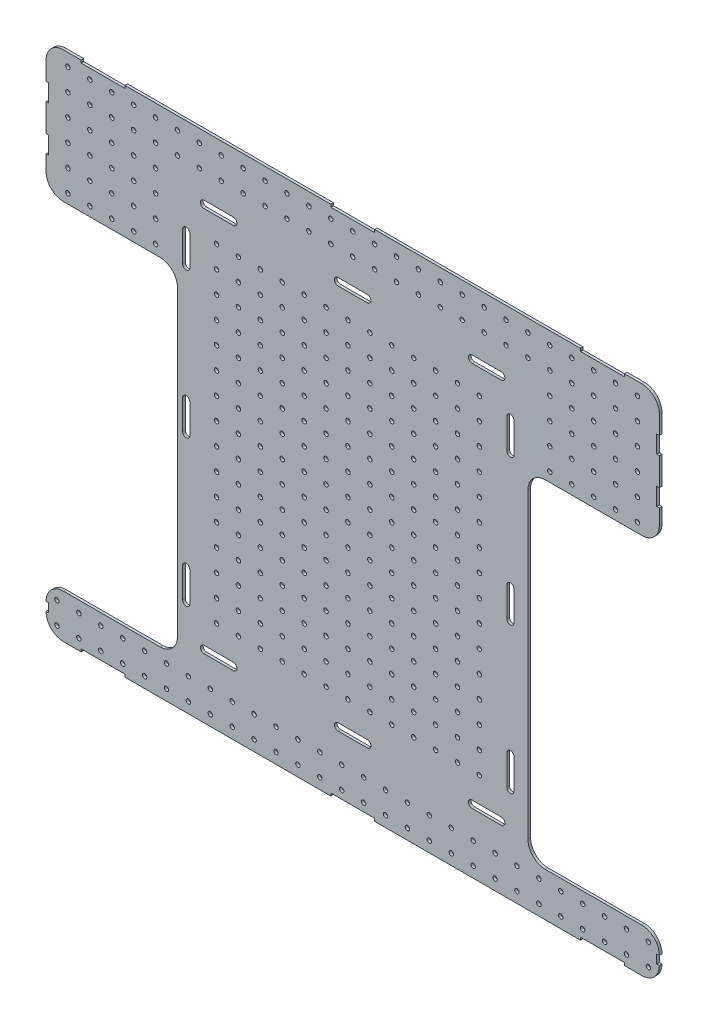
SolidWorks part; units mm, degrees
ref_plane "Front Plane" through (0, 0, 0) normal (0, 0, 1) x (1, 0, 0)
ref_plane "Top Plane" through (0, 0, 0) normal (0, 1, 0) x (1, 0, 0)
ref_plane "Right Plane" through (0, 0, 0) normal (1, 0, 0) x (0, 0, -1)
sketch "Sketch1" plane through (0, 0, 0) normal (0, 0, 1) x (1, 0, 0)
  line L0 (-330, 142.5) -> (-220, 142.5)
  line L1 (-330, -292.5) -> (330, -292.5)
  line L2 (-350, -272.5) -> (-350, -262.5)
  line L3 (-330, 292.5) -> (330, 292.5)
  line L4 (350, -272.5) -> (350, -262.5)
  line L5 (-350, -292.5) -> (-200, -167.1429) construction
  line L6 (-350, 292.5) -> (-343.6073, 287.1575) construction
  line L7 (-330, -242.5) -> (-220, -242.5)
  line L8 (-200, 122.5) -> (-200, -222.5)
  line L9 (200, 122.5) -> (200, -222.5)
  line L10 (220, 142.5) -> (330, 142.5)
  line L11 (220, -242.5) -> (330, -242.5)
  line L12 (-350, 162.5) -> (-350, 272.5)
  line L13 (350, 162.5) -> (350, 272.5)
  line L14 (343.6073, 287.1575) -> (350, 292.5) construction
  line L16 (-200, 122.5) -> (-200, -222.5)
  line L18 (200, 122.5) -> (200, -222.5)
  line L19 (200, -167.1429) -> (350, -292.5) construction
  line L20 (0, 0) -> (165.5771, 138.3751) construction
  line L21 (-101.0703, 84.4659) -> (18.5141, -15.4725) construction
  arc A0 (350, -262.5) -> (330, -242.5) centre (330, -262.5) ccw
  arc A1 (350, -272.5) -> (330, -292.5) centre (330, -272.5) cw
  arc A2 (-330, -292.5) -> (-350, -272.5) centre (-330, -272.5) cw
  arc A3 (-350, -262.5) -> (-330, -242.5) centre (-330, -262.5) cw
  arc A4 (-220, -242.5) -> (-200, -222.5) centre (-220, -222.5) ccw
  arc A5 (200, -222.5) -> (220, -242.5) centre (220, -222.5) ccw
  arc A6 (200, 122.5) -> (220, 142.5) centre (220, 122.5) cw
  arc A7 (350, 162.5) -> (330, 142.5) centre (330, 162.5) cw
  arc A8 (350, 272.5) -> (330, 292.5) centre (330, 272.5) ccw
  arc A9 (-200, 122.5) -> (-220, 142.5) centre (-220, 122.5) ccw
  arc A10 (-330, 142.5) -> (-350, 162.5) centre (-330, 162.5) cw
  arc A11 (-350, 272.5) -> (-330, 292.5) centre (-330, 272.5) cw
  circle A29 centre (-65.0414, 139.6103) radius 2
  circle A30 centre (-35.0414, 139.6103) radius 2
  circle A31 centre (-5.0415, 139.6103) radius 2
  circle A32 centre (24.9585, 139.6103) radius 2
  circle A33 centre (54.9585, 139.6103) radius 2
  circle A34 centre (84.9585, 139.6103) radius 2
  circle A35 centre (114.9584, 139.6103) radius 2
  circle A36 centre (144.9584, 139.6103) radius 2
  circle A41 centre (-95.0827, 108.0718) radius 2
  circle A42 centre (-65.0827, 108.0718) radius 2
  circle A43 centre (-35.0827, 108.0718) radius 2
  circle A44 centre (-5.0827, 108.0718) radius 2
  circle A45 centre (24.9172, 108.0718) radius 2
  circle A46 centre (54.9172, 108.0718) radius 2
  circle A47 centre (84.9172, 108.0718) radius 2
  circle A48 centre (114.9172, 108.0718) radius 2
  circle A49 centre (144.9171, 108.0718) radius 2
  circle A52 centre (-155.1239, 76.5334) radius 2
  circle A53 centre (-125.1239, 76.5334) radius 2
  circle A54 centre (-99.9787, 82.7901) radius 2
  circle A55 centre (-65.124, 76.5334) radius 2
  circle A56 centre (-35.124, 76.5334) radius 2
  circle A57 centre (-5.124, 76.5334) radius 2
  circle A58 centre (24.8759, 76.5334) radius 2
  circle A59 centre (54.8759, 76.5334) radius 2
  circle A60 centre (84.8759, 76.5334) radius 2
  circle A61 centre (114.8759, 76.5334) radius 2
  circle A62 centre (144.8758, 76.5334) radius 2
  circle A65 centre (-155.1652, 44.9949) radius 2
  circle A66 centre (-125.1652, 44.9949) radius 2
  circle A67 centre (-95.1653, 44.9949) radius 2
  circle A68 centre (-65.1653, 44.9949) radius 2
  circle A69 centre (-35.1653, 44.9949) radius 2
  circle A70 centre (-5.1653, 44.9949) radius 2
  circle A71 centre (24.8346, 44.9949) radius 2
  circle A72 centre (54.8346, 44.9949) radius 2
  circle A73 centre (84.8346, 44.9949) radius 2
  circle A74 centre (114.8346, 44.9949) radius 2
  circle A75 centre (144.8345, 44.9949) radius 2
  circle A78 centre (-155.2065, 13.4565) radius 2
  circle A79 centre (-125.2065, 13.4565) radius 2
  circle A80 centre (-95.2065, 13.4565) radius 2
  circle A81 centre (-65.2066, 13.4565) radius 2
  circle A82 centre (-35.2066, 13.4565) radius 2
  circle A83 centre (-5.2066, 13.4565) radius 2
  circle A84 centre (24.7933, 13.4565) radius 2
  circle A85 centre (54.7933, 13.4565) radius 2
  circle A86 centre (84.7933, 13.4565) radius 2
  circle A87 centre (114.7933, 13.4565) radius 2
  circle A88 centre (144.7932, 13.4565) radius 2
  circle A91 centre (-155.2478, -18.082) radius 2
  circle A92 centre (-125.2478, -18.082) radius 2
  circle A93 centre (-95.2478, -18.082) radius 2
  circle A94 centre (-65.2479, -18.082) radius 2
  circle A95 centre (-35.2479, -18.082) radius 2
  circle A96 centre (-5.2479, -18.082) radius 2
  circle A97 centre (18.5779, -13.4735) radius 2
  circle A98 centre (54.752, -18.082) radius 2
  circle A99 centre (84.752, -18.082) radius 2
  circle A100 centre (114.752, -18.082) radius 2
  circle A101 centre (144.7519, -18.082) radius 2
  circle A104 centre (-155.2891, -49.6205) radius 2
  circle A105 centre (-125.2891, -49.6205) radius 2
  circle A106 centre (-95.2891, -49.6205) radius 2
  circle A107 centre (-65.2892, -49.6205) radius 2
  circle A108 centre (-35.2892, -49.6205) radius 2
  circle A109 centre (-5.2892, -49.6205) radius 2
  circle A110 centre (24.7108, -49.6205) radius 2
  circle A111 centre (54.7107, -49.6205) radius 2
  circle A112 centre (84.7107, -49.6205) radius 2
  circle A113 centre (114.7107, -49.6205) radius 2
  circle A114 centre (144.7107, -49.6205) radius 2
  circle A117 centre (-155.3304, -81.1589) radius 2
  circle A118 centre (-125.3304, -81.1589) radius 2
  circle A119 centre (-95.3304, -81.1589) radius 2
  circle A120 centre (-65.3305, -81.1589) radius 2
  circle A121 centre (-35.3305, -81.1589) radius 2
  circle A122 centre (-5.3305, -81.1589) radius 2
  circle A123 centre (24.6695, -81.1589) radius 2
  circle A124 centre (54.6694, -81.1589) radius 2
  circle A125 centre (84.6694, -81.1589) radius 2
  circle A126 centre (114.6694, -81.1589) radius 2
  circle A127 centre (144.6694, -81.1589) radius 2
  circle A130 centre (-155.3717, -112.6974) radius 2
  circle A131 centre (-125.3717, -112.6974) radius 2
  circle A132 centre (-95.3717, -112.6974) radius 2
  circle A133 centre (-65.3718, -112.6974) radius 2
  circle A134 centre (-35.3718, -112.6974) radius 2
  circle A135 centre (-5.3718, -112.6974) radius 2
  circle A136 centre (24.6282, -112.6974) radius 2
  circle A137 centre (54.6281, -112.6974) radius 2
  circle A138 centre (84.6281, -112.6974) radius 2
  circle A139 centre (114.6281, -112.6974) radius 2
  circle A140 centre (144.6281, -112.6974) radius 2
  circle A143 centre (-155.413, -144.2358) radius 2
  circle A144 centre (-125.413, -144.2358) radius 2
  circle A145 centre (-95.413, -144.2358) radius 2
  circle A146 centre (-65.413, -144.2358) radius 2
  circle A147 centre (-35.4131, -144.2358) radius 2
  circle A148 centre (-5.4131, -144.2358) radius 2
  circle A149 centre (24.5869, -144.2358) radius 2
  circle A150 centre (54.5869, -144.2358) radius 2
  circle A151 centre (84.5868, -144.2358) radius 2
  circle A152 centre (114.5868, -144.2358) radius 2
  circle A153 centre (144.5868, -144.2358) radius 2
  circle A156 centre (-155.4543, -175.7743) radius 2
  circle A157 centre (-125.4543, -175.7743) radius 2
  circle A158 centre (-95.4543, -175.7743) radius 2
  circle A159 centre (-65.4543, -175.7743) radius 2
  circle A160 centre (-35.4544, -175.7743) radius 2
  circle A161 centre (-5.4544, -175.7743) radius 2
  circle A162 centre (24.5456, -175.7743) radius 2
  circle A163 centre (54.5456, -175.7743) radius 2
  circle A164 centre (84.5455, -175.7743) radius 2
  circle A165 centre (114.5455, -175.7743) radius 2
  circle A166 centre (144.5455, -175.7743) radius 2
  point P0 (0, 0)
  point P32 (350, 142.5)
  point P40 (-350, 142.5)
  dimension "D6" = 20
  dimension "D7" = 150
  dimension "D1" = 585
  dimension "D2" = 400
  dimension "D3" = 150
  dimension "D4" = 50
  dimension "D5" = 150
extrude "Boss-Extrude1" add sketch "Sketch1" along normal blind 3 contours A11 L12 A10 L0 A9 L8 A4 L7 A3 L2 A2 L1 A1 L4 A0 L11 A5 L9 A6 L10 A7 L13 A8 L3 region at (-0.0004, 19.8849, 0)
sketch "Sketch2" plane through (0, 0, 3) normal (0, 0, 1) x (1, 0, 0)
  line L0 (0, 292.5) -> (0, 224.1) construction
  line L1 (-330, 292.5) -> (330, 292.5) construction
  line L2 (-330, -292.5) -> (330, -292.5) construction
  line L3 (-200, 220) -> (-173.742, 220)
  line L4 (-200, 240) -> (200, 240)
  line L5 (-200, 240) -> (-200, -240)
  line L6 (-200, -240) -> (200, -240)
  line L7 (200, 240) -> (200, -240)
  line L8 (-200, 240) -> (200, -240) construction
  line L9 (-200, -240) -> (200, 240) construction
  line L10 (-200, -220) -> (-173.742, -220)
  line L11 (-169.642, 224.1) -> (-136.2091, 224.1)
  line L12 (169.642, 224.1) -> (136.2091, 224.1)
  line L13 (-169.642, 215.9) -> (-136.2091, 215.9)
  line L14 (169.642, 215.9) -> (136.2091, 215.9)
  line L15 (-132.1091, 220) -> (-20.815, 220)
  line L16 (0, 0) -> (200, 0) construction
  line L17 (200, 0) -> (-185.9, 0) construction
  line L18 (169.642, -215.9) -> (136.2091, -215.9)
  line L19 (169.642, -224.1) -> (136.2091, -224.1)
  line L20 (-169.642, -224.1) -> (-136.2091, -224.1)
  line L21 (-169.642, -215.9) -> (-136.2091, -215.9)
  line L22 (173.742, 220) -> (200, 220)
  line L23 (173.742, -220) -> (200, -220)
  line L24 (-132.1091, -220) -> (132.1091, -220)
  line L25 (-190, -240) -> (-190, -16.715) construction
  line L26 (-190, 220) -> (0, 0) construction
  line L27 (-194.1, 183.2958) -> (-194.1, 149.131)
  line L29 (-185.9, 183.2958) -> (-185.9, 149.131)
  line L31 (-190, 166.2134) -> (-190, 240) construction
  line L32 (180, 240) -> (180, -240) construction
  line L33 (-190, 50.3433) -> (180, 50.3433) construction
  line L34 (180, 50.3433) -> (-5, 50.3433) construction
  line L35 (-5, 50.3433) -> (-5, 153.231) construction
  line L36 (175.9, 183.2958) -> (175.9, 149.131)
  line L37 (184.1, 183.2958) -> (184.1, 149.131)
  line L38 (-185.9, -183.2958) -> (-185.9, -149.131)
  line L39 (-194.1, -183.2958) -> (-194.1, -149.131)
  line L40 (175.9, -183.2958) -> (175.9, -149.131)
  line L41 (184.1, -183.2958) -> (184.1, -149.131)
  line L42 (-16.715, 224.1) -> (32.477, 224.1) construction
  line L43 (-16.715, 224.1) -> (16.715, 224.1)
  line L44 (-16.715, 215.9) -> (16.715, 215.9)
  line L45 (-16.715, -224.1) -> (16.715, -224.1)
  line L46 (0, 215.9) -> (0, -292.5) construction
  line L47 (20.815, 220) -> (132.1091, 220)
  line L48 (-16.715, -215.9) -> (16.715, -215.9)
  line L49 (184.1, 16.715) -> (184.1, -16.715)
  line L50 (-194.1, 16.715) -> (-194.1, -16.715)
  line L52 (-185.9, 16.715) -> (-185.9, -16.715)
  line L54 (-194.1, 0) -> (-200, 0) construction
  line L55 (-190, 20.815) -> (-190, 153.231) construction
  line L56 (175.9, 16.715) -> (175.9, -16.715)
  arc A0 (-169.642, 224.1) -> (-169.642, 215.9) centre (-169.642, 220) ccw
  arc A1 (-136.2091, 215.9) -> (-136.2091, 224.1) centre (-136.2091, 220) ccw
  arc A2 (136.2091, 215.9) -> (136.2091, 224.1) centre (136.2091, 220) cw
  arc A3 (169.642, 224.1) -> (169.642, 215.9) centre (169.642, 220) cw
  arc A4 (169.642, -224.1) -> (169.642, -215.9) centre (169.642, -220) ccw
  arc A5 (136.2091, -215.9) -> (136.2091, -224.1) centre (136.2091, -220) ccw
  arc A6 (-136.2091, -215.9) -> (-136.2091, -224.1) centre (-136.2091, -220) cw
  arc A7 (-169.642, -224.1) -> (-169.642, -215.9) centre (-169.642, -220) cw
  arc A9 (-185.9, 183.2958) -> (-194.1, 183.2958) centre (-190, 183.2958) ccw
  arc A10 (-194.1, 149.131) -> (-185.9, 149.131) centre (-190, 149.131) ccw
  arc A13 (175.9, 183.2958) -> (184.1, 183.2958) centre (180, 183.2958) cw
  arc A14 (184.1, 149.131) -> (175.9, 149.131) centre (180, 149.131) cw
  arc A15 (-185.9, -183.2958) -> (-194.1, -183.2958) centre (-190, -183.2958) cw
  arc A16 (-194.1, -149.131) -> (-185.9, -149.131) centre (-190, -149.131) cw
  arc A17 (184.1, -149.131) -> (175.9, -149.131) centre (180, -149.131) ccw
  arc A18 (175.9, -183.2958) -> (184.1, -183.2958) centre (180, -183.2958) ccw
  arc A19 (-16.715, 224.1) -> (-16.715, 215.9) centre (-16.715, 220) ccw
  arc A20 (16.715, 215.9) -> (16.715, 224.1) centre (16.715, 220) ccw
  arc A21 (16.715, -215.9) -> (16.715, -224.1) centre (16.715, -220) cw
  arc A22 (-16.715, -224.1) -> (-16.715, -215.9) centre (-16.715, -220) cw
  arc A23 (-185.9, 16.715) -> (-194.1, 16.715) centre (-190, 16.715) ccw
  arc A24 (-194.1, -16.715) -> (-185.9, -16.715) centre (-190, -16.715) ccw
  arc A25 (175.9, 16.715) -> (184.1, 16.715) centre (180, 16.715) cw
  arc A26 (184.1, -16.715) -> (175.9, -16.715) centre (180, -16.715) cw
  point P6 (0, 0)
  point P91 (0, 224.1)
  point P107 (-190, 0)
  dimension "D5" = 8.2
  dimension "D6" = 8.2
  dimension "D8" = 8.2
  dimension "D9" = 8.2
  dimension "D12" = 8.2
  dimension "D1" = 400
  dimension "D2" = 480
  dimension "D3" = 20
  dimension "D4" = 20
  dimension "D7" = 20
  dimension "D10" = 20
  dimension "D11" = 33.43
  dimension "D13" = 33.43
extrude "Cut-Extrude1" cut sketch "Sketch2" against normal blind 3 contours A1 L11 A0 L13 | L27 A10 L29 A9 | A3 L12 A2 L14 | A14 L37 A13 L36 | L18 A5 L19 A4 | L40 A18 L41 A17 | A16 L39 A15 L38 | A7 L20 A6 L21 | L50 A24 L52 A23 | A26 L49 A25 L56 | A22 L45 A21 L24 | A22 L24 A21 L48 | A20 L43 A19 L44 region at (-152.9255, 220, 3) region at (-152.9255, -220, 3) region at (152.9255, 220, 3) region at (0, 220, 3) region at (152.9255, -220, 3) region at (0, -218.0001, 3) region at (0, -221.9999, 3) region at (-190, 166.2134, 3) region at (180, 166.2134, 3) region at (-190, -166.2134, 3) region at (180, -166.2134, 3) region at (180, 0, 3) region at (-190, 0, 3)
sketch "Sketch3" plane through (0, 0, 3) normal (0, 0, 1) x (1, 0, 0)
  line L0 (-330, 292.5) -> (330, 292.5) construction
  line L1 (-310, 292.5) -> (-260, 292.5)
  line L2 (-310, 292.5) -> (-310, 289.5)
  line L3 (-310, 289.5) -> (-260, 289.5)
  line L4 (-260, 292.5) -> (-260, 289.5)
  line L5 (-350, 162.5) -> (-350, 272.5) construction
  line L6 (-25, 292.5) -> (25, 292.5)
  line L7 (-25, 292.5) -> (-25, 289.5)
  line L8 (-25, 289.5) -> (25, 289.5)
  line L9 (25, 292.5) -> (25, 289.5)
  line L10 (310, 292.5) -> (260, 292.5)
  line L11 (310, 292.5) -> (310, 289.5)
  line L12 (310, 289.5) -> (260, 289.5)
  line L13 (260, 292.5) -> (260, 289.5)
  line L14 (350, 162.5) -> (350, 272.5) construction
  line L15 (0, 0) -> (0, 248.4856) construction
  line L16 (-350, 251.3627) -> (-347, 251.3627)
  line L17 (-350, 251.3627) -> (-350, 231.3627)
  line L18 (-350, 231.3627) -> (-347, 231.3627)
  line L19 (-347, 251.3627) -> (-347, 231.3627)
  line L20 (350, 231.3627) -> (347, 231.3627)
  line L21 (347, 251.3627) -> (347, 231.3627)
  line L22 (350, 251.3627) -> (347, 251.3627)
  line L23 (350, 251.3627) -> (350, 231.3627)
  line L24 (0, 0) -> (-127.5021, 0) construction
  line L25 (310, -289.5) -> (260, -289.5)
  line L26 (260, -292.5) -> (260, -289.5)
  line L27 (310, -292.5) -> (260, -292.5)
  line L28 (310, -292.5) -> (310, -289.5)
  line L29 (-25, -289.5) -> (25, -289.5)
  line L30 (25, -292.5) -> (25, -289.5)
  line L31 (-25, -292.5) -> (25, -292.5)
  line L32 (-25, -292.5) -> (-25, -289.5)
  line L33 (-310, -289.5) -> (-260, -289.5)
  line L34 (-260, -292.5) -> (-260, -289.5)
  line L35 (-310, -292.5) -> (-260, -292.5)
  line L36 (-310, -292.5) -> (-310, -289.5)
  line L37 (350, 179.7944) -> (347, 179.7944)
  line L38 (-350, -262.5) -> (-347, -262.5)
  line L39 (-350, -262.5) -> (-350, -272.5)
  line L40 (-350, -272.5) -> (-347, -272.5)
  line L41 (-347, -262.5) -> (-347, -272.5)
  line L42 (350, -262.5) -> (347, -262.5)
  line L43 (350, -262.5) -> (350, -272.5)
  line L44 (350, -272.5) -> (347, -272.5)
  line L45 (347, -262.5) -> (347, -272.5)
  line L46 (-350, 199.7944) -> (-347, 199.7944)
  line L47 (-350, 199.7944) -> (-350, 179.7944)
  line L48 (-350, 179.7944) -> (-347, 179.7944)
  line L49 (-347, 199.7944) -> (-347, 179.7944)
  line L50 (347, 199.7944) -> (347, 179.7944)
  line L51 (350, 199.7944) -> (347, 199.7944)
  line L52 (350, 199.7944) -> (350, 179.7944)
  point P15 (0, 292.5)
  point P16 (0, 292.5)
  dimension "D1" = 3
  dimension "D2" = 50
  dimension "D3" = 40
  dimension "D4" = 40
  dimension "D5" = 20
  dimension "D6" = 3
  dimension "D7" = 3
  dimension "D8" = 3
  dimension "D9" = 10
  dimension "D10" = 10
  dimension "D11" = 20
extrude "Cut-Extrude2" cut sketch "Sketch3" against normal blind 3
sketch "Sketch4" plane through (0, 0, 3) normal (0, 0, 1) x (1, 0, 0)
  line L1 (-160.8973, -188.258) -> (160.8973, -188.258)
  line L2 (-160.8973, -188.258) -> (-160.8973, 188.258)
  line L3 (-160.8973, 188.258) -> (160.8973, 188.258)
  line L4 (160.8973, -188.258) -> (160.8973, 188.258)
  line L5 (-160.8973, -188.258) -> (160.8973, 188.258) construction
  line L6 (-160.8973, 188.258) -> (160.8973, -188.258) construction
  point P0 (0, 0)
extrude "Boss-Extrude2" add sketch "Sketch4" against normal blind 3
sketch "Sketch6" plane through (0, 0, 3) normal (0, 0, 1) x (1, 0, 0)
  line L0 (-340, 282.8883) -> (340, 282.1649) construction
  line L1 (340, 282.1649) -> (340, 152.5) construction
  line L2 (340, 152.5) -> (204.1, 152.5) construction
  line L3 (204.1, 152.5) -> (204.1, 244.1) construction
  line L4 (204.1, 244.1) -> (-214.1, 244.1) construction
  line L5 (-214.1, 244.1) -> (-214.1, 152.5) construction
  line L6 (-214.1, 152.5) -> (-340, 152.5) construction
  line L7 (-340, 152.5) -> (-340, 282.8883) construction
  line L8 (-169.642, 224.1) -> (-136.2091, 224.1) construction
  line L9 (-194.1, 183.2958) -> (-194.1, 149.131) construction
  line L10 (184.1, 183.2958) -> (184.1, 149.131) construction
  line L11 (220, 142.5) -> (330, 142.5) construction
  line L12 (-325, 278.1974) -> (-300, 278.1974) construction
  line L13 (350, 251.3627) -> (350, 272.5) construction
  line L16 (-330, 142.5) -> (-220, 142.5) construction
  circle A0 centre (-325, 278.1974) radius 2.55
  circle A1 centre (-300, 278.1974) radius 2.55
  circle A2 centre (-275, 278.1974) radius 2.55
  circle A3 centre (-250, 278.1974) radius 2.55
  circle A4 centre (-225, 278.1974) radius 2.55
  circle A5 centre (-200, 278.1974) radius 2.55
  circle A6 centre (-175, 278.1974) radius 2.55
  circle A7 centre (-150, 278.1974) radius 2.55
  circle A8 centre (-125, 278.1974) radius 2.55
  circle A9 centre (-100, 278.1974) radius 2.55
  circle A10 centre (-75, 278.1974) radius 2.55
  circle A11 centre (-50, 278.1974) radius 2.55
  circle A12 centre (-25, 278.1974) radius 2.55
  circle A13 centre (0, 278.1974) radius 2.55
  circle A14 centre (25, 278.1974) radius 2.55
  circle A15 centre (50, 278.1974) radius 2.55
  circle A16 centre (75, 278.1974) radius 2.55
  circle A17 centre (100, 278.1974) radius 2.55
  circle A18 centre (125, 278.1974) radius 2.55
  circle A19 centre (150, 278.1974) radius 2.55
  circle A20 centre (175, 278.1974) radius 2.55
  circle A21 centre (200, 278.1974) radius 2.55
  circle A22 centre (225, 278.1974) radius 2.55
  circle A23 centre (250, 278.1974) radius 2.55
  circle A24 centre (275, 278.1974) radius 2.55
  circle A25 centre (300, 278.1974) radius 2.55
  circle A26 centre (325, 278.1974) radius 2.55
  circle A30 centre (-300, 253.1974) radius 2.55
  circle A31 centre (-275, 253.1974) radius 2.55
  circle A32 centre (-250, 253.1974) radius 2.55
  circle A33 centre (-225, 253.1974) radius 2.55
  circle A34 centre (-200, 253.1974) radius 2.55
  circle A35 centre (-175, 253.1974) radius 2.55
  circle A36 centre (-150, 253.1974) radius 2.55
  circle A37 centre (-125, 253.1974) radius 2.55
  circle A38 centre (-100, 253.1974) radius 2.55
  circle A39 centre (-75, 253.1974) radius 2.55
  circle A40 centre (-50, 253.1974) radius 2.55
  circle A41 centre (-25, 253.1974) radius 2.55
  circle A42 centre (0, 253.1974) radius 2.55
  circle A43 centre (25, 253.1974) radius 2.55
  circle A44 centre (50, 253.1974) radius 2.55
  circle A45 centre (75, 253.1974) radius 2.55
  circle A46 centre (100, 253.1974) radius 2.55
  circle A47 centre (125, 253.1974) radius 2.55
  circle A48 centre (150, 253.1974) radius 2.55
  circle A49 centre (175, 253.1974) radius 2.55
  circle A50 centre (200, 253.1974) radius 2.55
  circle A51 centre (225, 253.1974) radius 2.55
  circle A52 centre (250, 253.1974) radius 2.55
  circle A53 centre (275, 253.1974) radius 2.55
  circle A54 centre (300, 253.1974) radius 2.55
  circle A55 centre (325, 253.1974) radius 2.55
  circle A59 centre (-325, 253.1974) radius 2.55
  circle A60 centre (-325, 228.1974) radius 2.55
  circle A61 centre (-300, 228.1974) radius 2.55
  circle A62 centre (-275, 228.1974) radius 2.55
  circle A63 centre (-250, 228.1974) radius 2.55
  circle A64 centre (-225, 228.1974) radius 2.55
  circle A72 centre (-325, 203.1974) radius 2.55
  circle A73 centre (-300, 203.1974) radius 2.55
  circle A74 centre (-275, 203.1974) radius 2.55
  circle A75 centre (-250, 203.1974) radius 2.55
  circle A76 centre (-225, 203.1974) radius 2.55
  circle A84 centre (-325, 178.1974) radius 2.55
  circle A85 centre (-300, 178.1974) radius 2.55
  circle A86 centre (-275, 178.1974) radius 2.55
  circle A87 centre (-250, 178.1974) radius 2.55
  circle A88 centre (-225, 178.1974) radius 2.55
  circle A96 centre (-325, 153.1974) radius 2.55
  circle A97 centre (-300, 153.1974) radius 2.55
  circle A98 centre (-275, 153.1974) radius 2.55
  circle A99 centre (-250, 153.1974) radius 2.55
  circle A100 centre (-225, 153.1974) radius 2.55
  circle A109 centre (300, 228.1974) radius 2.55 [skipped]
  circle A110 centre (325, 228.1974) radius 2.55 [skipped]
  circle A112 centre (300, 203.1974) radius 2.55 [skipped]
  circle A113 centre (325, 203.1974) radius 2.55 [skipped]
  circle A115 centre (300, 178.1974) radius 2.55 [skipped]
  circle A116 centre (325, 178.1974) radius 2.55 [skipped]
  circle A118 centre (300, 153.1974) radius 2.55 [skipped]
  circle A119 centre (325, 153.1974) radius 2.55 [skipped]
  circle A120 centre (225, 228.1974) radius 2.55
  circle A121 centre (250, 228.1974) radius 2.55
  circle A122 centre (275, 228.1974) radius 2.55
  circle A123 centre (300, 228.1974) radius 2.55
  circle A124 centre (325, 228.1974) radius 2.55
  circle A125 centre (225, 203.1974) radius 2.55
  circle A126 centre (250, 203.1974) radius 2.55
  circle A127 centre (275, 203.1974) radius 2.55
  circle A128 centre (300, 203.1974) radius 2.55
  circle A129 centre (325, 203.1974) radius 2.55
  circle A130 centre (225, 178.1974) radius 2.55
  circle A131 centre (250, 178.1974) radius 2.55
  circle A132 centre (275, 178.1974) radius 2.55
  circle A133 centre (300, 178.1974) radius 2.55
  circle A134 centre (325, 178.1974) radius 2.55
  circle A135 centre (225, 153.1974) radius 2.55
  circle A136 centre (250, 153.1974) radius 2.55
  circle A137 centre (275, 153.1974) radius 2.55
  circle A138 centre (300, 153.1974) radius 2.55
  circle A139 centre (325, 153.1974) radius 2.55
  circle A140 centre (-200, 228.1974) radius 2.55 [skipped]
  circle A141 centre (-200, 203.1974) radius 2.55 [skipped]
  circle A142 centre (-200, 178.1974) radius 2.55 [skipped]
  circle A143 centre (-200, 153.1974) radius 2.55 [skipped]
  point P24 (-275, 142.5)
  dimension "D9" = 5.1
  dimension "D1" = 20
  dimension "D2" = 20
  dimension "D3" = 20
  dimension "D4" = 10
  dimension "D5" = 10
  dimension "D6" = 10
  dimension "D7" = 10
  dimension "D8" = 10
  dimension "D13" = 25
  dimension "D14" = 15
  dimension "D15" = 5
  dimension "D10" = 27
  dimension "D11" = 2
  dimension "D12" = 5
extrude "Cut-Extrude4" cut sketch "Sketch6" against normal blind 3
sketch "Sketch7" plane through (0, 0, 3) normal (0, 0, 1) x (1, 0, 0)
  line L0 (-340, -253.1) -> (340, -253.1) construction
  line L1 (340, -253.1) -> (340, -282.5) construction
  line L2 (340, -282.5) -> (-340, -282.5) construction
  line L3 (-340, -282.5) -> (-340, -253.1) construction
  line L4 (-169.642, -224.1) -> (-136.2091, -224.1) construction
  line L5 (-260, -292.5) -> (-25, -292.5) construction
  circle A0 centre (-337.5159, -255.273) radius 2.55
  circle A1 centre (-312.5159, -255.273) radius 2.55
  circle A2 centre (-287.5159, -255.273) radius 2.55
  circle A3 centre (-262.5159, -255.273) radius 2.55
  circle A4 centre (-237.5159, -255.273) radius 2.55
  circle A5 centre (-212.5159, -255.273) radius 2.55
  circle A6 centre (-187.5159, -255.273) radius 2.55
  circle A7 centre (-162.5159, -255.273) radius 2.55
  circle A8 centre (-137.5159, -255.273) radius 2.55
  circle A9 centre (-112.5159, -255.273) radius 2.55
  circle A10 centre (-87.5159, -255.273) radius 2.55
  circle A11 centre (-62.5159, -255.273) radius 2.55
  circle A12 centre (-37.5159, -255.273) radius 2.55
  circle A13 centre (-12.5159, -255.273) radius 2.55
  circle A14 centre (12.4841, -255.273) radius 2.55
  circle A15 centre (37.4841, -255.273) radius 2.55
  circle A16 centre (62.4841, -255.273) radius 2.55
  circle A17 centre (87.4841, -255.273) radius 2.55
  circle A18 centre (112.4841, -255.273) radius 2.55
  circle A19 centre (137.4841, -255.273) radius 2.55
  circle A20 centre (162.4841, -255.273) radius 2.55
  circle A21 centre (187.4841, -255.273) radius 2.55
  circle A22 centre (212.4841, -255.273) radius 2.55
  circle A23 centre (237.4841, -255.273) radius 2.55
  circle A24 centre (262.4841, -255.273) radius 2.55
  circle A25 centre (287.4841, -255.273) radius 2.55
  circle A26 centre (312.4841, -255.273) radius 2.55
  circle A27 centre (337.4841, -255.273) radius 2.55
  circle A30 centre (-312.5159, -280.273) radius 2.55
  circle A31 centre (-287.5159, -280.273) radius 2.55
  circle A32 centre (-262.5159, -280.273) radius 2.55
  circle A33 centre (-237.5159, -280.273) radius 2.55
  circle A34 centre (-212.5159, -280.273) radius 2.55
  circle A35 centre (-187.5159, -280.273) radius 2.55
  circle A36 centre (-162.5159, -280.273) radius 2.55
  circle A37 centre (-137.5159, -280.273) radius 2.55
  circle A38 centre (-112.5159, -280.273) radius 2.55
  circle A39 centre (-87.5159, -280.273) radius 2.55
  circle A40 centre (-62.5159, -280.273) radius 2.55
  circle A41 centre (-37.5159, -280.273) radius 2.55
  circle A42 centre (-12.5159, -280.273) radius 2.55
  circle A43 centre (12.4841, -280.273) radius 2.55
  circle A44 centre (37.4841, -280.273) radius 2.55
  circle A45 centre (62.4841, -280.273) radius 2.55
  circle A46 centre (87.4841, -280.273) radius 2.55
  circle A47 centre (112.4841, -280.273) radius 2.55
  circle A48 centre (137.4841, -280.273) radius 2.55
  circle A49 centre (162.4841, -280.273) radius 2.55
  circle A50 centre (187.4841, -280.273) radius 2.55
  circle A51 centre (212.4841, -280.273) radius 2.55
  circle A52 centre (237.4841, -280.273) radius 2.55
  circle A53 centre (262.4841, -280.273) radius 2.55
  circle A54 centre (287.4841, -280.273) radius 2.55
  circle A55 centre (312.4841, -280.273) radius 2.55
  circle A56 centre (337.4841, -280.273) radius 2.55
  circle A59 centre (-337.5159, -280.273) radius 2.55
  point P8 (-337.442, -255.623)
  point P9 (-337.5159, -255.273)
  dimension "D5" = 5.1
  dimension "D1" = 29
  dimension "D2" = 10
  dimension "D3" = 28
  dimension "D6" = 2
extrude "Cut-Extrude5" cut sketch "Sketch7" against normal blind 3
sketch "Sketch8" plane through (0, 0, 3) normal (0, 0, 1) x (1, 0, 0)
  line L0 (-165.9, 195.9) -> (155.9, 195.9) construction
  line L1 (155.9, 195.9) -> (155.9, -195.9) construction
  line L2 (155.9, -195.9) -> (-165.9, -195.9) construction
  line L3 (-165.9, -195.9) -> (-165.9, 195.9) construction
  line L4 (-169.642, 215.9) -> (-136.2091, 215.9) construction
  line L5 (-185.9, 183.2958) -> (-185.9, 149.131) construction
  line L6 (175.9, 183.2958) -> (175.9, 149.131) construction
  line L7 (169.642, -215.9) -> (136.2091, -215.9) construction
  circle A0 centre (-155.4, 187.9) radius 2.55
  circle A1 centre (-130.4, 187.9) radius 2.55
  circle A2 centre (-105.4, 187.9) radius 2.55
  circle A3 centre (-80.4, 187.9) radius 2.55
  circle A4 centre (-55.4, 187.9) radius 2.55
  circle A5 centre (-30.4, 187.9) radius 2.55
  circle A6 centre (-5.4, 187.9) radius 2.55
  circle A7 centre (19.6, 187.9) radius 2.55
  circle A8 centre (44.6, 187.9) radius 2.55
  circle A9 centre (69.6, 187.9) radius 2.55
  circle A10 centre (94.6, 187.9) radius 2.55
  circle A11 centre (119.6, 187.9) radius 2.55
  circle A12 centre (144.6, 187.9) radius 2.55
  circle A14 centre (-130.4, 162.9) radius 2.55
  circle A15 centre (-105.4, 162.9) radius 2.55
  circle A16 centre (-80.4, 162.9) radius 2.55
  circle A17 centre (-55.4, 162.9) radius 2.55
  circle A18 centre (-30.4, 162.9) radius 2.55
  circle A19 centre (-5.4, 162.9) radius 2.55
  circle A20 centre (19.6, 162.9) radius 2.55
  circle A21 centre (44.6, 162.9) radius 2.55
  circle A22 centre (69.6, 162.9) radius 2.55
  circle A23 centre (94.6, 162.9) radius 2.55
  circle A24 centre (119.6, 162.9) radius 2.55
  circle A25 centre (144.6, 162.9) radius 2.55
  circle A27 centre (-130.4, 137.9) radius 2.55
  circle A28 centre (-105.4, 137.9) radius 2.55
  circle A29 centre (-80.4, 137.9) radius 2.55
  circle A30 centre (-55.4, 137.9) radius 2.55
  circle A31 centre (-30.4, 137.9) radius 2.55
  circle A32 centre (-5.4, 137.9) radius 2.55
  circle A33 centre (19.6, 137.9) radius 2.55
  circle A34 centre (44.6, 137.9) radius 2.55
  circle A35 centre (69.6, 137.9) radius 2.55
  circle A36 centre (94.6, 137.9) radius 2.55
  circle A37 centre (119.6, 137.9) radius 2.55
  circle A38 centre (144.6, 137.9) radius 2.55
  circle A40 centre (-130.4, 112.9) radius 2.55
  circle A41 centre (-105.4, 112.9) radius 2.55
  circle A42 centre (-80.4, 112.9) radius 2.55
  circle A43 centre (-55.4, 112.9) radius 2.55
  circle A44 centre (-30.4, 112.9) radius 2.55
  circle A45 centre (-5.4, 112.9) radius 2.55
  circle A46 centre (19.6, 112.9) radius 2.55
  circle A47 centre (44.6, 112.9) radius 2.55
  circle A48 centre (69.6, 112.9) radius 2.55
  circle A49 centre (94.6, 112.9) radius 2.55
  circle A50 centre (119.6, 112.9) radius 2.55
  circle A51 centre (144.6, 112.9) radius 2.55
  circle A53 centre (-130.4, 87.9) radius 2.55
  circle A54 centre (-105.4, 87.9) radius 2.55
  circle A55 centre (-80.4, 87.9) radius 2.55
  circle A56 centre (-55.4, 87.9) radius 2.55
  circle A57 centre (-30.4, 87.9) radius 2.55
  circle A58 centre (-5.4, 87.9) radius 2.55
  circle A59 centre (19.6, 87.9) radius 2.55
  circle A60 centre (44.6, 87.9) radius 2.55
  circle A61 centre (69.6, 87.9) radius 2.55
  circle A62 centre (94.6, 87.9) radius 2.55
  circle A63 centre (119.6, 87.9) radius 2.55
  circle A64 centre (144.6, 87.9) radius 2.55
  circle A66 centre (-130.4, 62.9) radius 2.55
  circle A67 centre (-105.4, 62.9) radius 2.55
  circle A68 centre (-80.4, 62.9) radius 2.55
  circle A69 centre (-55.4, 62.9) radius 2.55
  circle A70 centre (-30.4, 62.9) radius 2.55
  circle A71 centre (-5.4, 62.9) radius 2.55
  circle A72 centre (19.6, 62.9) radius 2.55
  circle A73 centre (44.6, 62.9) radius 2.55
  circle A74 centre (69.6, 62.9) radius 2.55
  circle A75 centre (94.6, 62.9) radius 2.55
  circle A76 centre (119.6, 62.9) radius 2.55
  circle A77 centre (144.6, 62.9) radius 2.55
  circle A79 centre (-130.4, 37.9) radius 2.55
  circle A80 centre (-105.4, 37.9) radius 2.55
  circle A81 centre (-80.4, 37.9) radius 2.55
  circle A82 centre (-55.4, 37.9) radius 2.55
  circle A83 centre (-30.4, 37.9) radius 2.55
  circle A84 centre (-5.4, 37.9) radius 2.55
  circle A85 centre (19.6, 37.9) radius 2.55
  circle A86 centre (44.6, 37.9) radius 2.55
  circle A87 centre (69.6, 37.9) radius 2.55
  circle A88 centre (94.6, 37.9) radius 2.55
  circle A89 centre (119.6, 37.9) radius 2.55
  circle A90 centre (144.6, 37.9) radius 2.55
  circle A92 centre (-130.4, 12.9) radius 2.55
  circle A93 centre (-105.4, 12.9) radius 2.55
  circle A94 centre (-80.4, 12.9) radius 2.55
  circle A95 centre (-55.4, 12.9) radius 2.55
  circle A96 centre (-30.4, 12.9) radius 2.55
  circle A97 centre (-5.4, 12.9) radius 2.55
  circle A98 centre (19.6, 12.9) radius 2.55
  circle A99 centre (44.6, 12.9) radius 2.55
  circle A100 centre (69.6, 12.9) radius 2.55
  circle A101 centre (94.6, 12.9) radius 2.55
  circle A102 centre (119.6, 12.9) radius 2.55
  circle A103 centre (144.6, 12.9) radius 2.55
  circle A105 centre (-130.4, -12.1) radius 2.55
  circle A106 centre (-105.4, -12.1) radius 2.55
  circle A107 centre (-80.4, -12.1) radius 2.55
  circle A108 centre (-55.4, -12.1) radius 2.55
  circle A109 centre (-30.4, -12.1) radius 2.55
  circle A110 centre (-5.4, -12.1) radius 2.55
  circle A111 centre (19.6, -12.1) radius 2.55
  circle A112 centre (44.6, -12.1) radius 2.55
  circle A113 centre (69.6, -12.1) radius 2.55
  circle A114 centre (94.6, -12.1) radius 2.55
  circle A115 centre (119.6, -12.1) radius 2.55
  circle A116 centre (144.6, -12.1) radius 2.55
  circle A118 centre (-130.4, -37.1) radius 2.55
  circle A119 centre (-105.4, -37.1) radius 2.55
  circle A120 centre (-80.4, -37.1) radius 2.55
  circle A121 centre (-55.4, -37.1) radius 2.55
  circle A122 centre (-30.4, -37.1) radius 2.55
  circle A123 centre (-5.4, -37.1) radius 2.55
  circle A124 centre (19.6, -37.1) radius 2.55
  circle A125 centre (44.6, -37.1) radius 2.55
  circle A126 centre (69.6, -37.1) radius 2.55
  circle A127 centre (94.6, -37.1) radius 2.55
  circle A128 centre (119.6, -37.1) radius 2.55
  circle A129 centre (144.6, -37.1) radius 2.55
  circle A131 centre (-130.4, -62.1) radius 2.55
  circle A132 centre (-105.4, -62.1) radius 2.55
  circle A133 centre (-80.4, -62.1) radius 2.55
  circle A134 centre (-55.4, -62.1) radius 2.55
  circle A135 centre (-30.4, -62.1) radius 2.55
  circle A136 centre (-5.4, -62.1) radius 2.55
  circle A137 centre (19.6, -62.1) radius 2.55
  circle A138 centre (44.6, -62.1) radius 2.55
  circle A139 centre (69.6, -62.1) radius 2.55
  circle A140 centre (94.6, -62.1) radius 2.55
  circle A141 centre (119.6, -62.1) radius 2.55
  circle A142 centre (144.6, -62.1) radius 2.55
  circle A144 centre (-130.4, -87.1) radius 2.55
  circle A145 centre (-105.4, -87.1) radius 2.55
  circle A146 centre (-80.4, -87.1) radius 2.55
  circle A147 centre (-55.4, -87.1) radius 2.55
  circle A148 centre (-30.4, -87.1) radius 2.55
  circle A149 centre (-5.4, -87.1) radius 2.55
  circle A150 centre (19.6, -87.1) radius 2.55
  circle A151 centre (44.6, -87.1) radius 2.55
  circle A152 centre (69.6, -87.1) radius 2.55
  circle A153 centre (94.6, -87.1) radius 2.55
  circle A154 centre (119.6, -87.1) radius 2.55
  circle A155 centre (144.6, -87.1) radius 2.55
  circle A157 centre (-130.4, -112.1) radius 2.55
  circle A158 centre (-105.4, -112.1) radius 2.55
  circle A159 centre (-80.4, -112.1) radius 2.55
  circle A160 centre (-55.4, -112.1) radius 2.55
  circle A161 centre (-30.4, -112.1) radius 2.55
  circle A162 centre (-5.4, -112.1) radius 2.55
  circle A163 centre (19.6, -112.1) radius 2.55
  circle A164 centre (44.6, -112.1) radius 2.55
  circle A165 centre (69.6, -112.1) radius 2.55
  circle A166 centre (94.6, -112.1) radius 2.55
  circle A167 centre (119.6, -112.1) radius 2.55
  circle A168 centre (144.6, -112.1) radius 2.55
  circle A170 centre (-130.4, -137.1) radius 2.55
  circle A171 centre (-105.4, -137.1) radius 2.55
  circle A172 centre (-80.4, -137.1) radius 2.55
  circle A173 centre (-55.4, -137.1) radius 2.55
  circle A174 centre (-30.4, -137.1) radius 2.55
  circle A175 centre (-5.4, -137.1) radius 2.55
  circle A176 centre (19.6, -137.1) radius 2.55
  circle A177 centre (44.6, -137.1) radius 2.55
  circle A178 centre (69.6, -137.1) radius 2.55
  circle A179 centre (94.6, -137.1) radius 2.55
  circle A180 centre (119.6, -137.1) radius 2.55
  circle A181 centre (144.6, -137.1) radius 2.55
  circle A183 centre (-130.4, -162.1) radius 2.55
  circle A184 centre (-105.4, -162.1) radius 2.55
  circle A185 centre (-80.4, -162.1) radius 2.55
  circle A186 centre (-55.4, -162.1) radius 2.55
  circle A187 centre (-30.4, -162.1) radius 2.55
  circle A188 centre (-5.4, -162.1) radius 2.55
  circle A189 centre (19.6, -162.1) radius 2.55
  circle A190 centre (44.6, -162.1) radius 2.55
  circle A191 centre (69.6, -162.1) radius 2.55
  circle A192 centre (94.6, -162.1) radius 2.55
  circle A193 centre (119.6, -162.1) radius 2.55
  circle A194 centre (144.6, -162.1) radius 2.55
  circle A196 centre (-130.4, -187.1) radius 2.55
  circle A197 centre (-105.4, -187.1) radius 2.55
  circle A198 centre (-80.4, -187.1) radius 2.55
  circle A199 centre (-55.4, -187.1) radius 2.55
  circle A200 centre (-30.4, -187.1) radius 2.55
  circle A201 centre (-5.4, -187.1) radius 2.55
  circle A202 centre (19.6, -187.1) radius 2.55
  circle A203 centre (44.6, -187.1) radius 2.55
  circle A204 centre (69.6, -187.1) radius 2.55
  circle A205 centre (94.6, -187.1) radius 2.55
  circle A206 centre (119.6, -187.1) radius 2.55
  circle A207 centre (144.6, -187.1) radius 2.55
  circle A222 centre (-155.4, 162.9) radius 2.55
  circle A223 centre (-155.4, 137.9) radius 2.55
  circle A224 centre (-155.4, 112.9) radius 2.55
  circle A225 centre (-155.4, 87.9) radius 2.55
  circle A226 centre (-155.4, 62.9) radius 2.55
  circle A227 centre (-155.4, 37.9) radius 2.55
  circle A228 centre (-155.4, 12.9) radius 2.55
  circle A229 centre (-155.4, -12.1) radius 2.55
  circle A230 centre (-155.4, -37.1) radius 2.55
  circle A231 centre (-155.4, -62.1) radius 2.55
  circle A232 centre (-155.4, -87.1) radius 2.55
  circle A233 centre (-155.4, -112.1) radius 2.55
  circle A234 centre (-155.4, -137.1) radius 2.55
  circle A235 centre (-155.4, -162.1) radius 2.55
  circle A236 centre (-155.4, -187.1) radius 2.55
  dimension "D5" = 5.1
  dimension "D1" = 20
  dimension "D2" = 20
  dimension "D3" = 20
  dimension "D4" = 20
  dimension "D6" = 10.5
  dimension "D7" = 8
  dimension "D9" = 13
  dimension "D8" = 16
extrude "Cut-Extrude6" cut sketch "Sketch8" against normal blind 3
